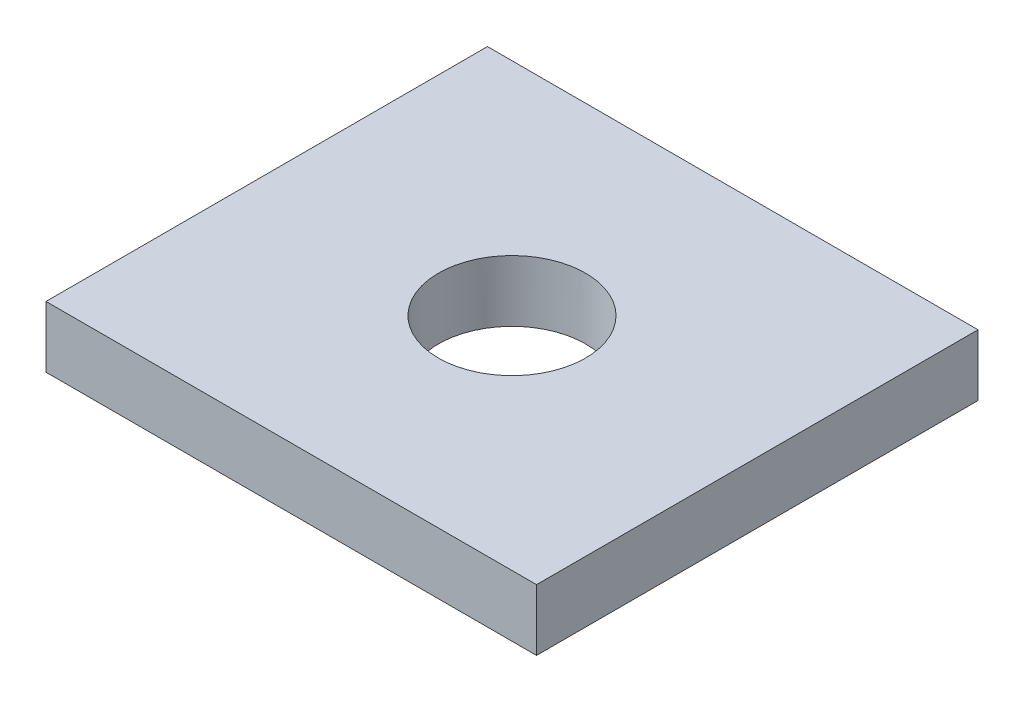
SolidWorks part; units mm, degrees
ref_plane "Front Plane" through (0, 0, 0) normal (0, 0, 1) x (1, 0, 0)
ref_plane "Top Plane" through (0, 0, 0) normal (0, 1, 0) x (1, 0, 0)
ref_plane "Right Plane" through (0, 0, 0) normal (1, 0, 0) x (0, 0, -1)
sketch "Sketch1" plane through (0, 0, 0) normal (0, 1, 0) x (1, 0, 0)
  line L1 (100, 90) -> (-100, 90)
  line L2 (100, 90) -> (100, -90)
  line L3 (100, -90) -> (-100, -90)
  line L4 (-100, 90) -> (-100, -90)
  line L5 (100, 90) -> (-100, -90) construction
  line L6 (100, -90) -> (-100, 90) construction
  point P0 (0, 0)
  dimension "D1" = 200
  dimension "D2" = 180
extrude "base" add sketch "Sketch1" along normal blind 25 contours L1 L4 L3 L2
sketch "Sketch2" plane through (0, 25, 0) normal (0, 1, 0) x (1, 0, 0)
  circle A0 centre (0, 0) radius 30
  dimension "D1" = 60
extrude "actuator cut" cut sketch "Sketch2" against normal blind 40
